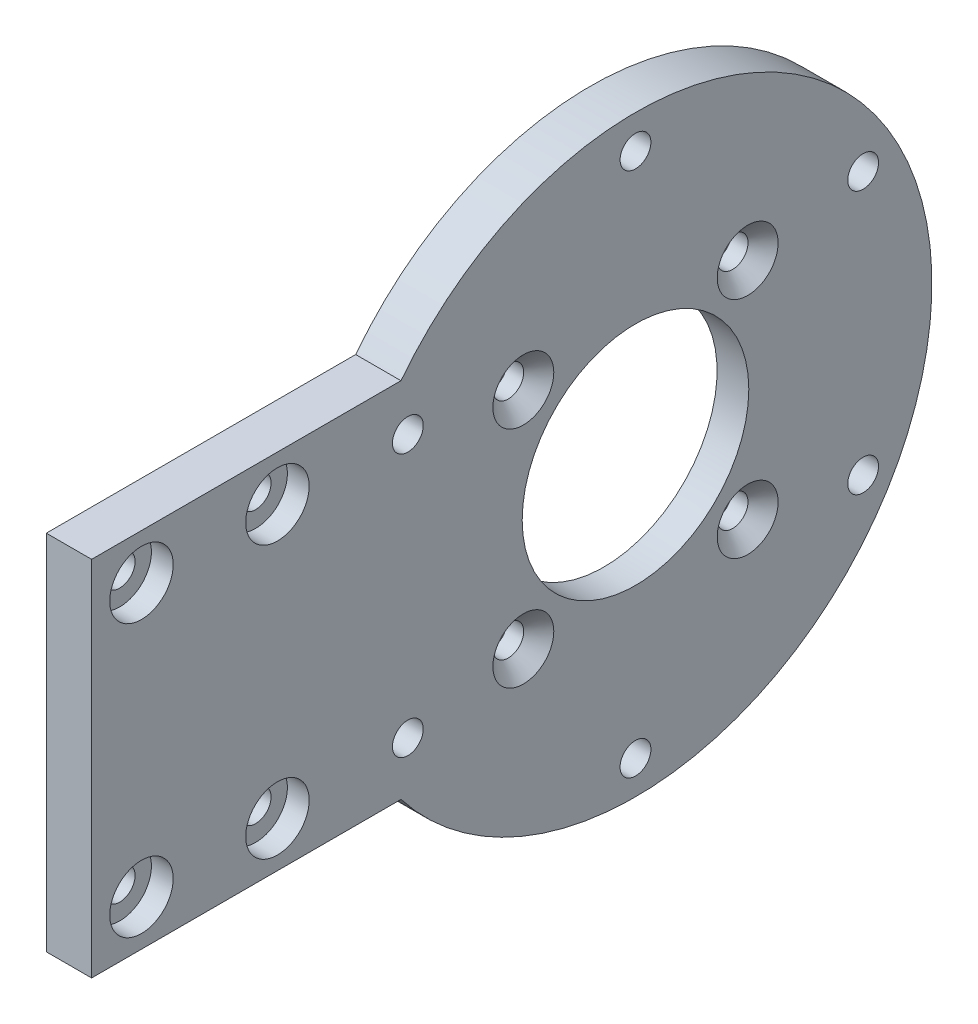
SolidWorks part; units mm, degrees
material "6063-T5"
ref_plane "Front" through (0, 0, 0) normal (0, 0, 1) x (1, 0, 0)
ref_plane "Top" through (0, 0, 0) normal (0, 1, 0) x (1, 0, 0)
ref_plane "Right" through (0, 0, 0) normal (1, 0, 0) x (0, 0, -1)
sketch "Croquis1" plane through (0, 0, 0) normal (1, 0, 0) x (0, 0, -1)
  line L0 (-25.8706, 20) -> (-60, 20)
  line L1 (-60, 20) -> (-60, -20)
  line L2 (-60, -20) -> (-25.8706, -20)
  line L3 (2.75, 0) -> (-2.75, 0) construction
  line L4 (0, 2.75) -> (0, -2.75) construction
  arc A0 (-25.8706, -20) -> (-25.8706, 20) centre (0, 0) ccw
  circle A1 centre (0, 0) radius 12.5
  point P7 (-60, 0)
  dimension "D1" = 65.4
  dimension "D4" = 25
  dimension "D2" = 40
  dimension "D3" = 60
extrude "Saliente-Extruir1" add sketch "Croquis1" along normal mid plane 5
sketch "Croquis2" plane through (-2.5, 0, 0) normal (-1, 0, 0) x (0, 0, 1)
  circle A0 centre (0, 0) radius 21
  dimension "D1" = 42
extrude "Cortar-Extruir1" cut sketch "Croquis2" against normal blind 1.5
hole_wizard "Refrentado para tornillo tapón con cabeza plana de clavija de M31" positions "Croquis3" profile "Croquis5" countersink size "M3" standard "Ansi Metric"
sketch "Croquis3" plane through (2.5, 0, 0) normal (1, 0, 0) x (0, 0, -1)
  line L1 (-12.3744, -12.3744) -> (12.3744, -12.3744) construction
  line L2 (-12.3744, -12.3744) -> (-12.3744, 12.3744) construction
  line L3 (-12.3744, 12.3744) -> (12.3744, 12.3744) construction
  line L4 (12.3744, -12.3744) -> (12.3744, 12.3744) construction
  line L5 (-12.3744, -12.3744) -> (12.3744, 12.3744) construction
  line L6 (-12.3744, 12.3744) -> (12.3744, -12.3744) construction
  point P2 (12.3744, 12.3744)
  point P39 (-12.3744, -12.3744)
  point P40 (-12.3744, 12.3744)
  point P41 (12.3744, -12.3744)
  dimension "D1" = 35
sketch "Croquis5" plane through (2.5, 12.3744, -12.3744) normal (0, 1, 0) x (0, 0, -1)
  line L0 (0, 0) -> (0, 11.0215)
  line L1 (0, 11.0215) -> (1.7, 10)
  line L2 (1.7, 10) -> (1.7, 1.66)
  line L3 (1.7, 1.66) -> (3.36, 0)
  line L5 (3.36, 0) -> (0, 0)
  line L6 (-1.7, 1.66) -> (-3.36, 0) construction
  line L10 (0, 11.0215) -> (-1.7, 10) construction
  line L11 (0, -6.35) -> (0, 107.95) construction
  dimension "Diámetro de taladro" = 3.4
  dimension "Profundidad de taladro" = 10
  dimension "Ángulo de avellanado cercano" = 6.72
  dimension "Ángulo de avellanado lejano" = 90
  dimension "Ángulo de perforador" = 118
hole_wizard "Taladro de margen para M31" positions "Croquis6" profile "Croquis8" hole size "M3" standard "Ansi Metric" end condition through all
sketch "Croquis6" plane through (2.5, 0, 0) normal (1, 0, 0) x (0, 0, -1)
  line L0 (0, 2.75) -> (0, -2.75) construction
  line L1 (2.75, 0) -> (-2.75, 0) construction
  point P0 (0, 29)
  point P11 (25.1147, 14.5)
  point P12 (25.1147, -14.5)
  point P13 (0, -29)
  point P14 (-25.1147, -14.5)
  point P15 (-25.1147, 14.5)
  dimension "D1" = 29
  dimension "D3" = 29
  dimension "D2" = 6
sketch "Croquis8" plane through (2.5, 29, 0) normal (0, 1, 0) x (0, 0, -1)
  line L0 (0, 0) -> (0, 5)
  line L1 (0, 5) -> (1.7, 5)
  line L2 (1.7, 5) -> (1.7, 0)
  line L5 (1.7, 0) -> (0, 0)
  line L11 (0, -6.35) -> (0, 107.95) construction
  dimension "Diámetro de taladro hasta el siguiente" = 3.4
  dimension "Profundidad de taladro hasta el siguiente" = 5
hole_wizard "Refrentado para tornillo con cabeza troncocónica de M31" positions "Croquis9" profile "Croquis11" counterbore size "M3" standard "Ansi Metric" end condition through all
sketch "Croquis9" plane through (2.5, 0, 0) normal (1, 0, 0) x (0, 0, -1)
  line L1 (-54.5, -15) -> (-39.5, -15) construction
  line L2 (-54.5, -15) -> (-54.5, 15) construction
  line L3 (-54.5, 15) -> (-39.5, 15) construction
  line L4 (-39.5, -15) -> (-39.5, 15) construction
  line L5 (-54.5, -15) -> (-39.5, 15) construction
  line L6 (-54.5, 15) -> (-39.5, -15) construction
  line L8 (2.75, 0) -> (-2.75, 0) construction
  line L9 (-60, 20) -> (-60, -20) construction
  point P2 (-39.5, 15)
  point P63 (-54.5, -15)
  point P64 (-54.5, 15)
  point P65 (-39.5, -15)
  point P74 (-47, 0)
  dimension "D1" = 30
  dimension "D2" = 15
  dimension "D3" = 13
sketch "Croquis11" plane through (2.5, 15, 39.5) normal (0, 1, 0) x (0, 0, -1)
  line L0 (0, 0) -> (0, 5)
  line L1 (0, 5) -> (1.7, 5)
  line L3 (1.7, 5) -> (1.7, 2.4)
  line L4 (1.7, 2.4) -> (3.5, 2.4)
  line L5 (3.5, 2.4) -> (3.5, 0)
  line L7 (3.5, 0) -> (0, 0)
  line L11 (0, -6.35) -> (0, 107.95) construction
  dimension "Diámetro de taladro hasta el siguiente" = 3.4
  dimension "Profundidad de taladro hasta el siguiente" = 5
  dimension "Diámetro de refrentado" = 7
  dimension "Profundidad de refrentado" = 2.4
